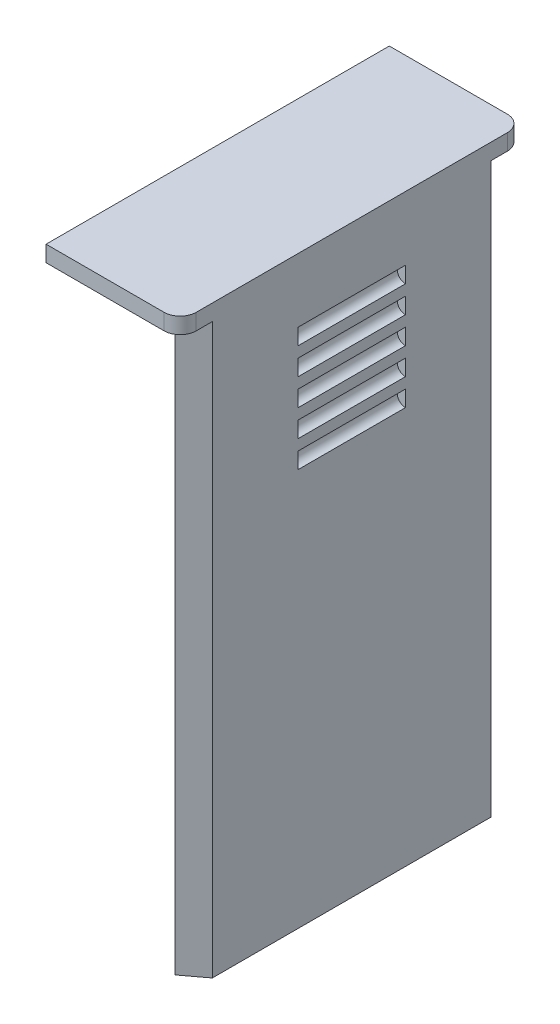
SolidWorks part; units mm, degrees
ref_plane "Alzado" through (0, 0, 0) normal (0, 0, 1) x (1, 0, 0)
ref_plane "Planta" through (0, 0, 0) normal (0, 1, 0) x (1, 0, 0)
ref_plane "Vista lateral" through (0, 0, 0) normal (1, 0, 0) x (0, 0, -1)
sketch "Croquis1" plane through (0, 111.4679, 0) normal (0, 1, 0) x (1, 0, 0)
  line L0 (-3.4522, -72.4184) -> (-15.9522, -72.4184)
  line L5 (-15.9522, -72.4184) -> (-15.9522, -104.4184)
  line L6 (-15.9522, -104.4184) -> (-3.4522, -104.4184)
  line L7 (-3.4522, -104.4184) -> (-3.4522, -72.4184)
  dimension "D1" = 12.5
  dimension "D2" = 32
extrude "Saliente-Extruir1" add sketch "Croquis1" against normal blind 1.5
sketch "Croquis2" plane through (0, 109.9679, 0) normal (0, -1, 0) x (1, 0, 0)
  line L0 (-3.4522, 101.4184) -> (-5.4522, 102.9184)
  line L3 (-3.4522, 104.4184) -> (-3.4522, 72.4184) construction
  line L4 (-15.9522, 88.4184) -> (1.8923, 88.4184) construction
  line L9 (-5.4522, 102.9184) -> (-5.4522, 73.9184)
  line L10 (-15.9522, 72.4184) -> (-15.9522, 104.4184) construction
  line L12 (-3.4522, 75.4184) -> (-3.4522, 101.4184)
  line L13 (-3.4522, 75.4184) -> (-5.4522, 73.9184)
  dimension "D1" = 2
  dimension "D2" = 2.5
  dimension "D3" = 29
extrude "Saliente-Extruir2" add sketch "Croquis2" along normal blind 53
ref_axis "Eje1" through (-3.4522, 111.4679, 88.4184) along (0, -1, 0)
ref_plane "Plano2" through (0, 0, 88.4184) normal (0, 0, 1) x (0, -1, 0)
sketch "Croquis4" plane through (0, 0, 88.4184) normal (0, 0, 1) x (0, -1, 0)
  line L0 (-104.7679, -3.4522) -> (-111.4679, -3.4522) construction
  line L1 (-111.4679, -3.4522) -> (-56.9679, -3.4522) construction
  circle A0 centre (-104.7679, -3.4522) radius 0.75
  circle A1 centre (-102.2679, -3.4522) radius 0.75
  circle A2 centre (-99.7679, -3.4522) radius 0.75
  circle A3 centre (-97.2679, -3.4522) radius 0.75
  circle A4 centre (-94.7679, -3.4522) radius 0.75
  dimension "D2" = 5
  dimension "D3" = 2.5
  dimension "D1" = 1.5
sketch "Croquis5" plane through (0, 109.9679, 0) normal (0, -1, 0) x (1, 0, 0)
  line L0 (-5.4522, 102.9184) -> (-5.4522, 73.9184) construction
  line L1 (-5.4522, 95.9184) -> (-6.4522, 95.9184)
  line L2 (-5.4522, 95.9184) -> (-5.4522, 80.9184)
  line L3 (-5.4522, 80.9184) -> (-6.4522, 80.9184)
  line L4 (-6.4522, 95.9184) -> (-6.4522, 80.9184)
  line L5 (-15.9522, 88.4184) -> (-5.4522, 88.4184) construction
  line L6 (-15.9522, 72.4184) -> (-15.9522, 104.4184) construction
  dimension "D1" = 15
  dimension "D2" = 1
extrude "Saliente-Extruir4" add sketch "Croquis5" along normal blind 20
extrude "Cortar-Extruir1" cut sketch "Croquis4" against normal mid plane 10
fillet "Redondeo1" radius 1.5 2 edges at (-3.4522, 110.7179, 72.4184) (-3.4522, 110.7179, 104.4184)
